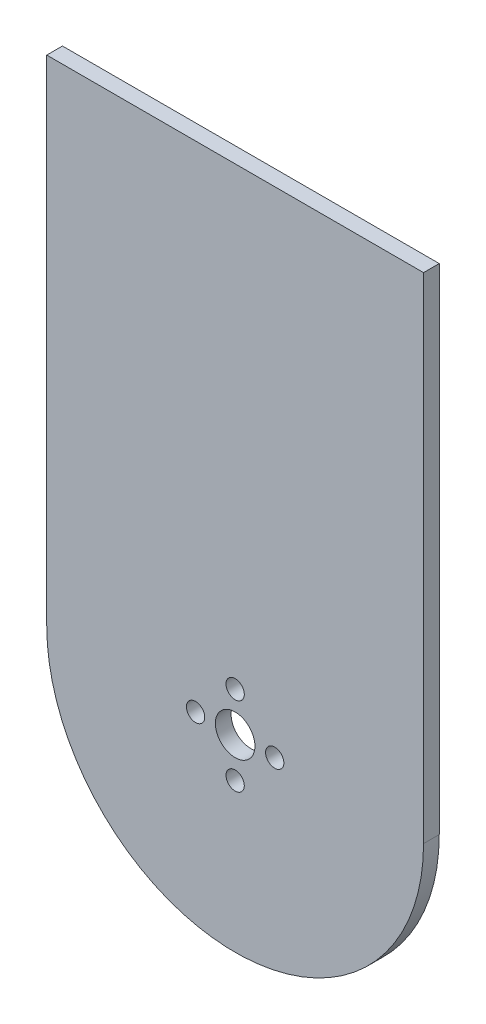
SolidWorks part; units mm, degrees
material "6061-T6 (SS)"
ref_plane "Front" through (0, 0, 0) normal (0, 0, 1) x (1, 0, 0)
ref_plane "Top" through (0, 0, 0) normal (0, 1, 0) x (1, 0, 0)
ref_plane "Right" through (0, 0, 0) normal (1, 0, 0) x (0, 0, -1)
ref_axis "side-side" through (80.9, 0, 0) along (-1, 0, 0)
ref_axis "up-down" through (0, 50, 0) along (0, -1, 0)
ref_axis "front-back" through (0, 0, -80.9) along (0, 0, 1)
sketch "Sketch1" plane through (0, 0, 0) normal (0, 0, 1) x (1, 0, 0)
  line L1 (-38.1, 100) -> (38.1, 100)
  line L2 (-38.1, 100) -> (-38.1, 0)
  line L3 (-38.1, 0) -> (38.1, 0) construction
  line L4 (38.1, 100) -> (38.1, 0)
  arc A0 (-38.1, 0) -> (38.1, 0) centre (0, 0) ccw
  circle A1 centre (0, 0) radius 4
  circle A2 centre (-8, 0) radius 1.85
  circle A3 centre (0, -8) radius 1.85
  circle A4 centre (0, 0) radius 8 construction
  circle A5 centre (0, 8) radius 1.85
  circle A6 centre (8, 0) radius 1.85
  dimension "D1" = 8
  dimension "D4" = 16
  dimension "D5" = 3.7
  dimension "D2" = 76.2
  dimension "D3" = 100
extrude "Boss-Extrude1" add sketch "Sketch1" along normal blind 3.175
